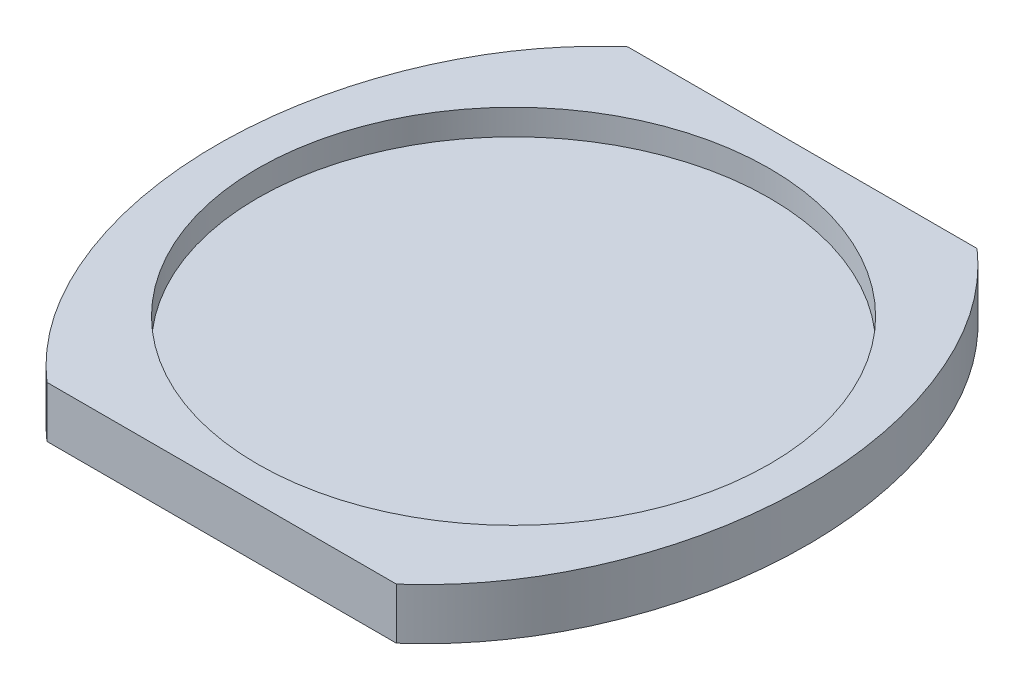
SolidWorks part; units mm, degrees
note: The reader was unsure of these and kept them because the rebuilt part matched: shared geometry of "Sketch1<3>".
material "ABS"
ref_plane "Front Plane" through (0, 0, 0) normal (0, 0, 1) x (1, 0, 0)
ref_plane "Top Plane" through (0, 0, 0) normal (0, 1, 0) x (1, 0, 0)
ref_plane "Right Plane" through (0, 0, 0) normal (1, 0, 0) x (0, 0, -1)
sketch "Sketch1" plane through (0, 0, 0) normal (0, 1, 0) x (1, 0, 0)
  line L2 (120, 140.0255) -> (120, -140.0255)
  line L3 (120, -140.0255) -> (0, -140.0255)
  line L4 (0, 140.0255) -> (0, -140.0255)
  line L5 (0, 140.0255) -> (120, 140.0255)
  circle A0 centre (0, 0) radius 100
  spline S0 degree 3 poles (-1.2053, -140.0255) (0.9208, -140.05) (3.0453, -140.0029) (7.2911, -139.7673) (9.3987, -139.5794) (15.6753, -138.812) (19.7991, -138.0298) (27.9298, -135.9433) (31.9367, -134.6391) (37.8597, -132.2925) (39.8042, -131.4509) (43.6236, -129.6592) (45.5005, -128.7082) (51.0358, -125.6947) (54.5996, -123.4728) (59.7647, -119.836) (61.4562, -118.5729) (63.9484, -116.6025) (64.7726, -115.9322) (66.3983, -114.5729) (67.2004, -113.8835) (71.1578, -110.3885) (74.1556, -107.44) (79.839, -101.2603) (82.5265, -98.0306) (86.3252, -92.9753) (87.5521, -91.2545) (89.9283, -87.7427) (91.0712, -85.9612) (93.2642, -82.358) (94.3155, -80.5349) (96.3299, -76.8467) (97.2919, -74.9811) (100.0571, -69.3269) (101.745, -65.4834) (104.0502, -59.6104) (104.7808, -57.6347) (106.1668, -53.6477) (106.8232, -51.6327) (108.67, -45.5667) (109.739, -41.494) (111.5667, -33.2937) (112.3254, -29.1661) (113.5382, -20.8569) (113.9923, -16.6754) (114.369, -11.4147) (114.4348, -10.3608) (114.5471, -8.2498) (114.5937, -7.1918) (114.704, -4.0239) (114.7387, -1.9166) (114.7212, 8.5965) (114.1001, 16.9334) (112.2634, 29.329) (111.4993, 33.4424) (110.1185, 39.5841) (109.3693, 42.6479) (108.5297, 45.7006) (107.9495, 47.7333) (107.6489, 48.7494) (106.1005, 53.8026) (104.7145, 57.7689) (101.6483, 65.5499) (99.9682, 69.3644) (97.2226, 74.9699) (96.2683, 76.8181) (94.2727, 80.4698) (93.2326, 82.2737) (89.9824, 87.6186) (87.6429, 91.0926) (84.4819, 95.313) (83.8377, 96.1509) (82.5255, 97.8143) (81.8566, 98.6412) (79.8221, 101.0937) (78.4305, 102.6889) (74.1493, 107.354) (71.1536, 110.304) (64.8674, 115.8706) (61.5767, 118.4871) (56.4048, 122.1451) (54.6414, 123.3199) (51.9341, 125.0117) (51.0237, 125.5624) (49.1937, 126.6329) (48.273, 127.1534) (43.6415, 129.682) (39.8462, 131.469) (32.073, 134.5656) (28.0951, 135.8751) (21.9833, 137.46) (19.9217, 137.9247) (16.7915, 138.5228) (15.7401, 138.7059) (13.635, 139.0366) (12.581, 139.1843) (7.3043, 139.8346) (3.0608, 140.0738) (-1.2053, 140.0255) knots 0 0 0 0 0.015625 0.015625 0.03125 0.03125 0.0625 0.0625 0.09375 0.09375 0.109375 0.109375 0.125 0.125 0.15625 0.15625 0.171875 0.171875 0.179687 0.179687 0.1875 0.1875 0.21875 0.21875 0.25 0.25 0.265625 0.265625 0.28125 0.28125 0.296875 0.296875 0.3125 0.3125 0.34375 0.34375 0.359375 0.359375 0.375 0.375 0.40625 0.40625 0.4375 0.4375 0.46875 0.46875 0.476563 0.476563 0.484375 0.484375 0.5 0.5 0.5625 0.5625 0.59375 0.59375 0.609375 0.617188 0.617188 0.625 0.625 0.65625 0.65625 0.6875 0.6875 0.703125 0.703125 0.71875 0.71875 0.75 0.75 0.757813 0.757813 0.765625 0.765625 0.78125 0.78125 0.8125 0.8125 0.84375 0.84375 0.859375 0.859375 0.867188 0.867188 0.875 0.875 0.90625 0.90625 0.9375 0.9375 0.953125 0.953125 0.960938 0.960938 0.96875 0.96875 1 1 1 1
  spline S1 degree 3 poles (0, 140.0255) (-2.1261, 140.05) (-4.2506, 140.0029) (-8.4964, 139.7673) (-10.604, 139.5794) (-16.8806, 138.812) (-21.0044, 138.0298) (-29.1351, 135.9433) (-33.142, 134.6391) (-39.065, 132.2925) (-41.0095, 131.4509) (-44.8288, 129.6592) (-46.7058, 128.7082) (-52.2411, 125.6947) (-55.8049, 123.4728) (-60.9699, 119.836) (-62.6614, 118.5729) (-65.1537, 116.6025) (-65.9779, 115.9322) (-67.6036, 114.5729) (-68.4057, 113.8835) (-72.3631, 110.3885) (-75.3609, 107.44) (-81.0443, 101.2603) (-83.7318, 98.0306) (-87.5305, 92.9753) (-88.7574, 91.2545) (-91.1336, 87.7427) (-92.2764, 85.9612) (-94.4695, 82.358) (-95.5208, 80.5349) (-97.5352, 76.8467) (-98.4972, 74.9811) (-101.2623, 69.3269) (-102.9503, 65.4834) (-105.2555, 59.6104) (-105.9861, 57.6347) (-107.3721, 53.6477) (-108.0285, 51.6327) (-109.8753, 45.5667) (-110.9442, 41.494) (-112.772, 33.2937) (-113.5307, 29.1661) (-114.7435, 20.8569) (-115.1976, 16.6754) (-115.5743, 11.4147) (-115.6401, 10.3608) (-115.7524, 8.2498) (-115.7989, 7.1918) (-115.9093, 4.0239) (-115.944, 1.9166) (-115.9265, -8.5965) (-115.3054, -16.9334) (-113.4687, -29.329) (-112.7046, -33.4424) (-111.3238, -39.5841) (-110.5746, -42.6479) (-109.735, -45.7006) (-109.1548, -47.7333) (-108.8542, -48.7494) (-107.3058, -53.8026) (-105.9198, -57.7689) (-102.8536, -65.5499) (-101.1735, -69.3644) (-98.4279, -74.9699) (-97.4735, -76.8181) (-95.478, -80.4698) (-94.4379, -82.2737) (-91.1876, -87.6186) (-88.8481, -91.0926) (-85.6872, -95.313) (-85.0429, -96.1509) (-83.7307, -97.8143) (-83.0619, -98.6412) (-81.0274, -101.0937) (-79.6358, -102.6889) (-75.3546, -107.354) (-72.3589, -110.304) (-66.0726, -115.8706) (-62.7819, -118.4871) (-57.6101, -122.1451) (-55.8467, -123.3199) (-53.1394, -125.0117) (-52.229, -125.5624) (-50.3989, -126.6329) (-49.4783, -127.1534) (-44.8468, -129.682) (-41.0515, -131.469) (-33.2783, -134.5656) (-29.3004, -135.8751) (-23.1886, -137.46) (-21.127, -137.9247) (-17.9968, -138.5228) (-16.9454, -138.7059) (-14.8403, -139.0366) (-13.7863, -139.1843) (-8.5096, -139.8346) (-4.2661, -140.0738) (0, -140.0255) knots 0 0 0 0 0.015625 0.015625 0.03125 0.03125 0.0625 0.0625 0.09375 0.09375 0.109375 0.109375 0.125 0.125 0.15625 0.15625 0.171875 0.171875 0.179687 0.179687 0.1875 0.1875 0.21875 0.21875 0.25 0.25 0.265625 0.265625 0.28125 0.28125 0.296875 0.296875 0.3125 0.3125 0.34375 0.34375 0.359375 0.359375 0.375 0.375 0.40625 0.40625 0.4375 0.4375 0.46875 0.46875 0.476563 0.476563 0.484375 0.484375 0.5 0.5 0.5625 0.5625 0.59375 0.59375 0.609375 0.617188 0.617188 0.625 0.625 0.65625 0.65625 0.6875 0.6875 0.703125 0.703125 0.71875 0.71875 0.75 0.75 0.757813 0.757813 0.765625 0.765625 0.78125 0.78125 0.8125 0.8125 0.84375 0.84375 0.859375 0.859375 0.867188 0.867188 0.875 0.875 0.90625 0.90625 0.9375 0.9375 0.953125 0.953125 0.960938 0.960938 0.96875 0.96875 1 1 1 1
  point P9 (0, 0)
  dimension "D3" = 200
  dimension "D2" = 280.0511
extrude "Boss-Extrude1" add sketch "Sketch1" along normal mid plane 20 contours A0 L4 L3 L2 L5 | L4 S1 A0
extrude "Boss-Extrude2" add sketch "Sketch1<3>" against normal up to surface (10 mm away) contours A0 | L4 A0 up to face at (0, -10, 100)
sketch "Sketch1<3>" plane through (0, 0, 0) normal (0, 1, 0) x (1, 0, 0) same geometry as "Sketch1"
sketch "Sketch2" plane through (0, 10, 0) normal (0, 1, 0) x (1, 0, 0)
  line L1 (98.6213, -181.4403) -> (98.6213, -113.461)
  line L6 (-115.9407, 0) -> (120, 0) construction
  line L9 (-115.9407, 181.4403) -> (98.6213, 181.4403)
  line L10 (-115.9407, 181.4403) -> (-115.9407, 113.461)
  line L11 (-115.9407, 113.461) -> (98.6213, 113.461)
  line L12 (98.6213, 181.4403) -> (98.6213, 113.461)
  line L13 (-115.9407, -113.461) -> (98.6213, -113.461)
  line L14 (-115.9407, -181.4403) -> (-115.9407, -113.461)
  line L15 (-115.9407, -181.4403) -> (98.6213, -181.4403)
extrude "Cut-Extrude1" cut sketch "Sketch2" against normal through all both and the other way through all
